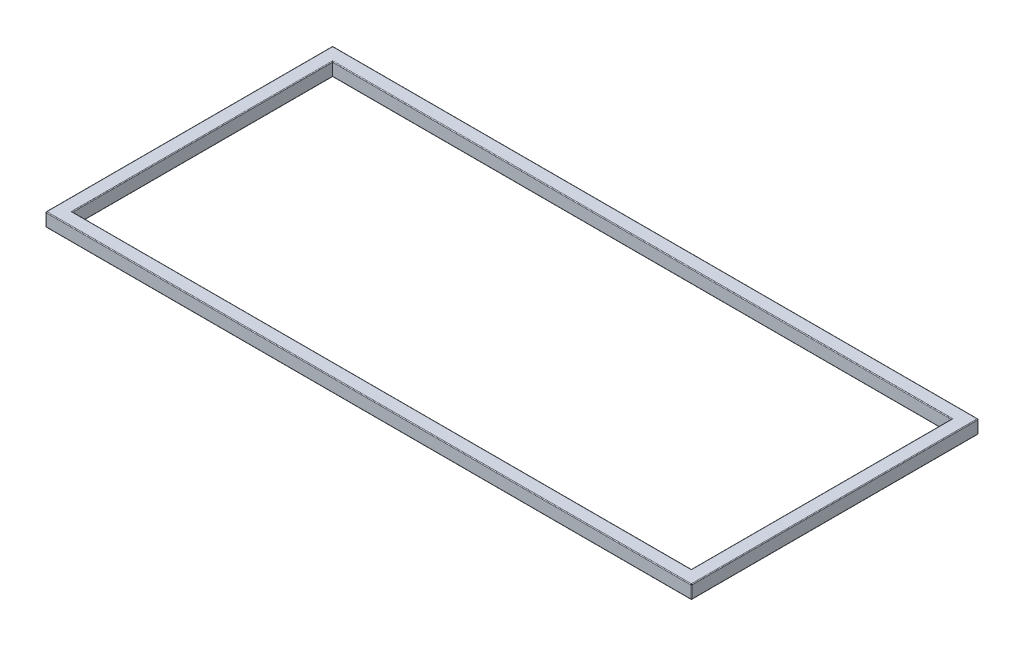
SolidWorks part; units mm, degrees
material "1023 Carbon Steel Sheet (SS)"
ref_plane "Front Plane" through (0, 0, 0) normal (0, 0, 1) x (1, 0, 0)
ref_plane "Top Plane" through (0, 0, 0) normal (0, 1, 0) x (1, 0, 0)
ref_plane "Right Plane" through (0, 0, 0) normal (1, 0, 0) x (0, 0, -1)
sketch "Sketch1" plane through (0, 0, 0) normal (0, 1, 0) x (1, 0, 0)
  line L1 (-438.15, -184.15) -> (438.15, -184.15)
  line L2 (-438.15, -184.15) -> (-438.15, 184.15)
  line L3 (-438.15, 184.15) -> (438.15, 184.15)
  line L4 (438.15, -184.15) -> (438.15, 184.15)
  line L5 (-438.15, -184.15) -> (438.15, 184.15) construction
  line L6 (-438.15, 184.15) -> (438.15, -184.15) construction
  line L7 (-457.2, -203.2) -> (457.2, -203.2)
  line L8 (-457.2, -203.2) -> (-457.2, 203.2)
  line L9 (-457.2, 203.2) -> (457.2, 203.2)
  line L10 (457.2, -203.2) -> (457.2, 203.2)
  line L11 (-457.2, -203.2) -> (457.2, 203.2) construction
  line L12 (-457.2, 203.2) -> (457.2, -203.2) construction
  point P0 (0, 0)
  point P6 (0, 0)
  dimension "D1" = 914.4
  dimension "D2" = 406.4
  dimension "D3" = 19.05
  dimension "D4" = 19.05
extrude "Boss-Extrude1" add sketch "Sketch1" along normal blind 19.05
fillet "Fillet1" radius 1.016 16 edges at (-438.15, 0, 0) (0, 0, -184.15) (438.15, 0, 0) (0, 0, 184.15) (0, 0, -203.2) (-457.2, 0, 0) (0, 0, 203.2) (457.2, 0, 0) (0, 19.05, -184.15) (-438.15, 19.05, 0) (0, 19.05, 184.15) (438.15, 19.05, 0) (0, 19.05, 203.2) (-457.2, 19.05, 0) (0, 19.05, -203.2) (457.2, 19.05, 0)
fillet "Fillet2" radius 1.016 12 edges at (456.9024, 18.7524, 202.9024) (456.9024, 0.2976, 202.9024) (-456.9024, 18.7524, 202.9024) (-456.9024, 0.2976, 202.9024) (-456.9024, 18.7524, -202.9024) (-456.9024, 0.2976, -202.9024) (456.9024, 18.7524, -202.9024) (456.9024, 0.2976, -202.9024) (457.2, 9.525, 203.2) (-457.2, 9.525, 203.2) (-457.2, 9.525, -203.2) (457.2, 9.525, -203.2)
